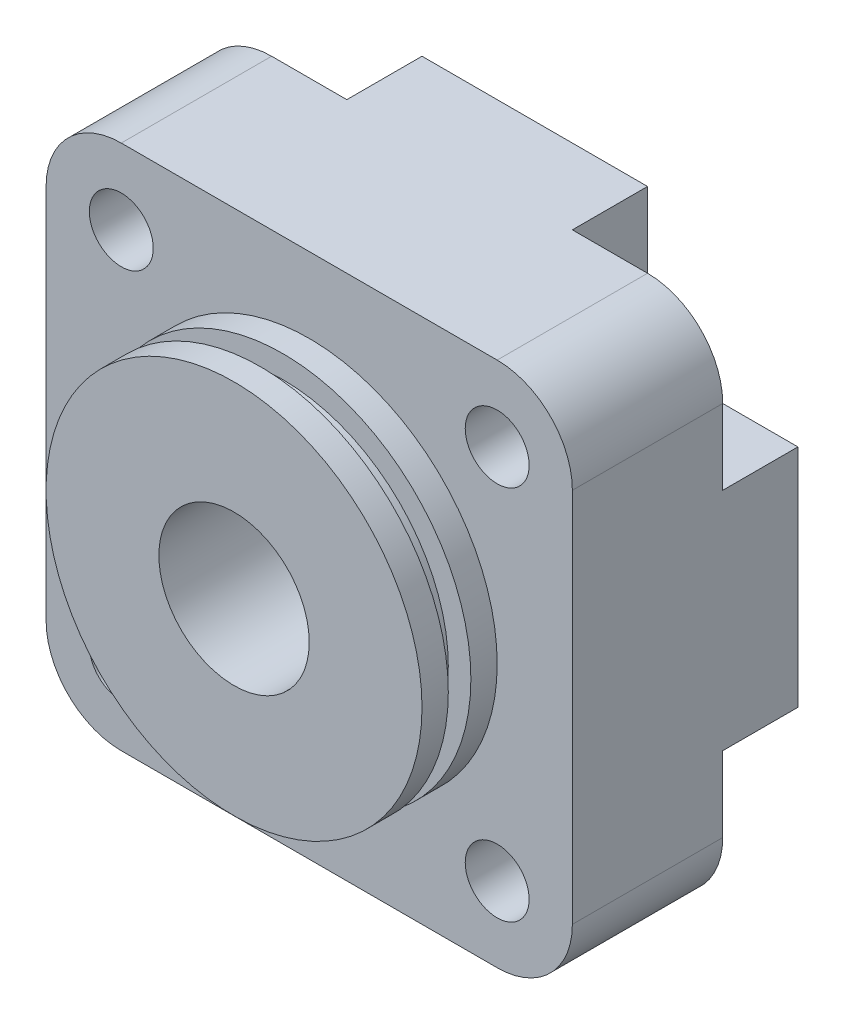
SolidWorks part; units mm, degrees
ref_plane "Front Plane" through (0, 0, 0) normal (0, 0, 1) x (1, 0, 0)
ref_plane "Top Plane" through (0, 0, 0) normal (0, 1, 0) x (1, 0, 0)
ref_plane "Right Plane" through (0, 0, 0) normal (1, 0, 0) x (0, 0, -1)
sketch "Sketch1" plane through (0, 0, 0) normal (0, 0, 1) x (1, 0, 0)
  line L1 (35, -35) -> (-35, -35)
  line L2 (35, -35) -> (35, 35)
  line L3 (35, 35) -> (-35, 35)
  line L4 (-35, -35) -> (-35, 35)
  line L5 (35, -35) -> (-35, 35) construction
  line L6 (35, 35) -> (-35, -35) construction
  point P0 (0, 0)
  dimension "D1" = 70
extrude "Boss-Extrude1" add sketch "Sketch1" along normal blind 30
sketch "Sketch2" plane through (0, 0, 30) normal (0, 0, 1) x (1, 0, 0)
  circle A0 centre (0, 0) radius 25
  dimension "D1" = 50
extrude "Boss-Extrude2" add sketch "Sketch2" along normal blind 3.5
sketch "Sketch3" plane through (0, 0, 33.5) normal (0, 0, 1) x (1, 0, 0)
  circle A0 centre (0, 0) radius 22
  dimension "D1" = 44
extrude "Boss-Extrude3" add sketch "Sketch3" along normal blind 3
sketch "Sketch4" plane through (0, 0, 36.5) normal (0, 0, 1) x (1, 0, 0)
  circle A0 centre (0, 0) radius 25
  dimension "D1" = 50
extrude "Boss-Extrude4" add sketch "Sketch4" along normal blind 3.5
sketch "Sketch5" plane through (0, 0, 0) normal (0, 0, -1) x (-1, 0, 0)
  line L0 (-15, 35) -> (-15, 15)
  line L1 (-35, 35) -> (35, 35) construction
  line L2 (-15, 15) -> (-35, 15)
  line L3 (-35, -35) -> (-35, 35) construction
  circle A0 centre (-25, 25) radius 4.25
  line M2 (35, 35) -> (-35, 35)
  line M3 (-35, 35) -> (-35, -35)
  dimension "D3" = 10
  dimension "D5" = 8.5
  dimension "D1" = 20
  dimension "D2" = 20
  dimension "D4" = 10
extrude "Cut-Extrude1" cut sketch "Sketch5" against normal up to next contours A0 region at (25, 25, 0)
extrude "Cut-Extrude2" cut sketch "Sketch5<3>" against normal blind 10 contours L2 L0 A0 M2 M3 region at (15.2828, 25, 0)
sketch "Sketch5<3>" plane through (0, 0, 0) normal (0, 0, -1) x (-1, 0, 0) same geometry as "Sketch5"
fillet "Fillet1" radius 10 2 edges at (15, 15, 5) (35, 35, 20)
fillet "Fillet2" radius 10 3 edges at (-35, 35, 15) (-35, -35, 15) (35, -35, 15)
sketch "Sketch7" plane through (0, 0, 40) normal (0, 0, 1) x (1, 0, 0)
  circle A0 centre (0, 0) radius 10
  dimension "D1" = 20
extrude "Cut-Extrude3" cut sketch "Sketch7" against normal blind 30
sketch "Sketch8" plane through (-35, 0, 0) normal (-1, 0, 0) x (0, 0, 1)
  line L0 (0, 0) -> (30, 0) construction
  line L1 (30, 25) -> (30, -25) construction
  circle A0 centre (15, 0) radius 9
  dimension "D2" = 18
  dimension "D1" = 15
extrude "Cut-Extrude4" cut sketch "Sketch8" against normal blind 2
mirror "Mirror5" about plane through (0, 0, 0) normal (0, 1, 0) of "Cut-Extrude2", "Cut-Extrude1"
mirror "Mirror6" about plane through (0, 0, 0) normal (1, 0, 0) of "Cut-Extrude1", "Mirror5", "Cut-Extrude2"
fillet "Fillet3" radius 10 3 edges at (-15, 15, 5) (-15, -15, 5) (15, -15, 5)
hole_wizard "M14 Tapped Hole1" positions "Sketch12" profile "Sketch11" tap size "M14" standard "DIN"
sketch "Sketch12" plane through (-33, 0, 0) normal (-1, 0, 0) x (0, 0, 1)
  line L0 (0, 0) -> (24, 0) construction
  line L2 (15, 0) -> (15, 9) construction
  circle A0 centre (15, 0) radius 9 construction
  point P0 (15, 0)
sketch "Sketch11" plane through (-33, 0, 15) normal (0, 1, 0) x (0, 0, 1)
  line L0 (0, 0) -> (0, 15.6052)
  line L1 (0, 15.6052) -> (6, 12)
  line L2 (6, 12) -> (6, 0)
  line L5 (6, 0) -> (0, 0)
  line L10 (0, 15.6052) -> (-6, 12) construction
  line L11 (0, -6.35) -> (0, 107.95) construction
  dimension "Tap Drill Dia." = 12
  dimension "Tap Drill Depth" = 12
  dimension "Drill Angle" = 118
cosmetic thread "Hole Thread1" parameters "D1"=10, "D2"=14
chamfer "Chamfer1" distance 1 angle 45 1 edges at (-33, 0, 21)
sketch "Sketch13" plane through (-33, 0, 0) normal (-1, 0, 0) x (0, 0, 1)
  circle A0 centre (15, 0) radius 3
  dimension "D1" = 6
extrude "Cut-Extrude5" cut sketch "Sketch13" against normal up to next
ref_plane "Plane1" through (0, 0, 35) normal (0, 0, 1) x (1, 0, 0)
